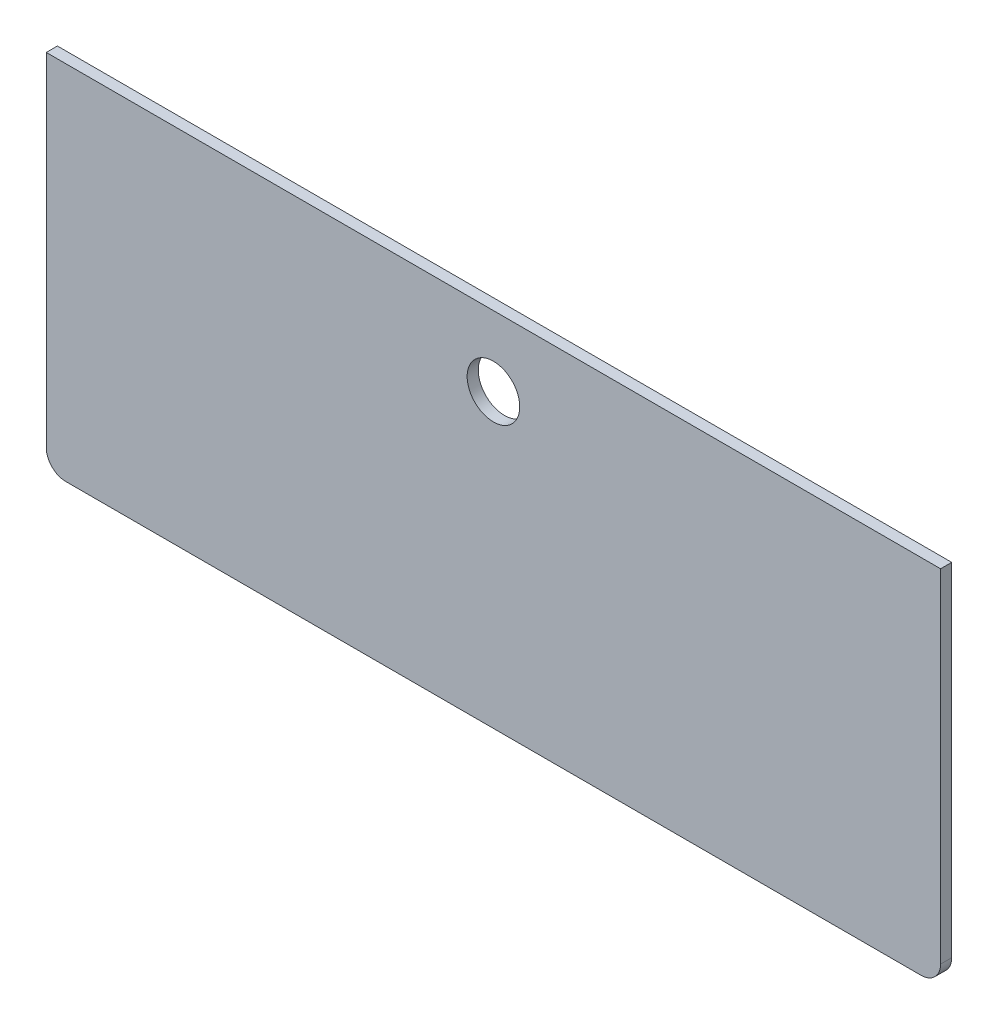
SolidWorks part; units mm, degrees
material "5052-H32"
ref_plane "Front Plane" through (0, 0, 0) normal (0, 0, 1) x (1, 0, 0)
ref_plane "Top Plane" through (0, 0, 0) normal (0, 1, 0) x (1, 0, 0)
ref_plane "Right Plane" through (0, 0, 0) normal (1, 0, 0) x (0, 0, -1)
sketch "Sketch1" plane through (0, 0, 0) normal (0, 0, 1) x (1, 0, 0)
  line L0 (-151.7654, 27.1868) -> (-151.7654, -75.9882)
  line L1 (-151.7654, -75.9882) -> (103.2346, -75.9882)
  line L2 (103.2346, -75.9882) -> (103.2346, 27.1868)
  line L3 (103.2346, 27.1868) -> (-151.7654, 27.1868)
  line L4 (-24.2654, 27.1868) -> (-24.2654, 7.1868) construction
  circle A0 centre (-24.2654, 7.1868) radius 7.5
  dimension "D4" = 15
  dimension "D1" = 103.175
  dimension "D2" = 255
  dimension "D3" = 20
extrude "Boss-Extrude1" add sketch "Sketch1" along normal blind 3.175
fillet "Fillet1" radius 5.5562 2 edges at (-151.7654, -75.9882, 1.5875) (103.2346, -75.9882, 1.5875)
equation "\"L\"= 385"
equation "\"W\"= 255"
equation "\"H\"= 110"
equation "\"Compartment Width\"= 80"
equation "\"T\"= 4.7625 * 2 / 3"
equation "\"Inside Fillet Radius\"= 5.55625"
equation "\"D1@Boss-Extrude1\"=\"T\""
equation "\"D1@Fillet1\"=\"Inside Fillet Radius\""
equation "\"Hole\"=15"
equation "\"D4@Sketch1\"=\"Hole\""
equation "\"D2@Sketch1\"=\"W\""
equation "\"D1@Sketch1\"=\"H\"+\"T\"-10"
equation "\"Offset\"= 30"
equation "\"Wheel to Wall\"= 50"
